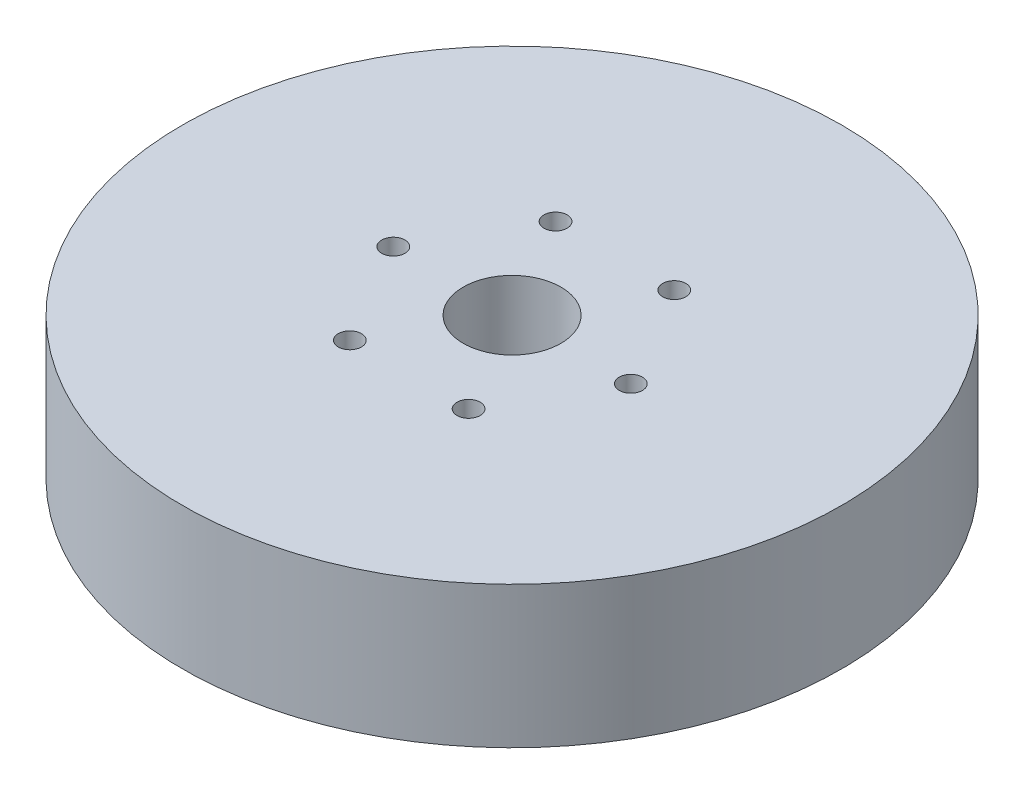
SolidWorks part; units mm, degrees
ref_plane "Front Plane" through (0, 0, 0) normal (0, 0, 1) x (1, 0, 0)
ref_plane "Top Plane" through (0, 0, 0) normal (0, 1, 0) x (1, 0, 0)
ref_plane "Right Plane" through (0, 0, 0) normal (1, 0, 0) x (0, 0, -1)
sketch "Sketch1" plane through (0, 0, 0) normal (0, 1, 0) x (1, 0, 0)
  circle A0 centre (0, 0) radius 67.5
  dimension "FLANGE_OD" = 135
extrude "Boss-Extrude1" add sketch "Sketch1" along normal blind 29
sketch "Sketch2" plane through (0, 0, 0) normal (0, 1, 0) x (1, 0, 0)
  circle A0 centre (0, 0) radius 10
  dimension "BORE_D" = 20
extrude "Cut-Extrude1" cut sketch "Sketch2" along normal through all
sketch "Sketch3" plane through (0, 29, 0) normal (0, 1, 0) x (1, 0, 0)
  circle A0 centre (0, 0) radius 24.3225 construction
  circle A1 centre (-24.3225, 0) radius 2.3751
  dimension "BOLT_D" = 4.7502
  dimension "BOLT_PCD" = 48.6449
extrude "Cut-Extrude2" cut sketch "Sketch3" against normal blind 18.4024
pattern_circular "CirPattern1" count 6 over 360 about axis through (0, 0, 0) along (0, 1, 0) of "Cut-Extrude2"
